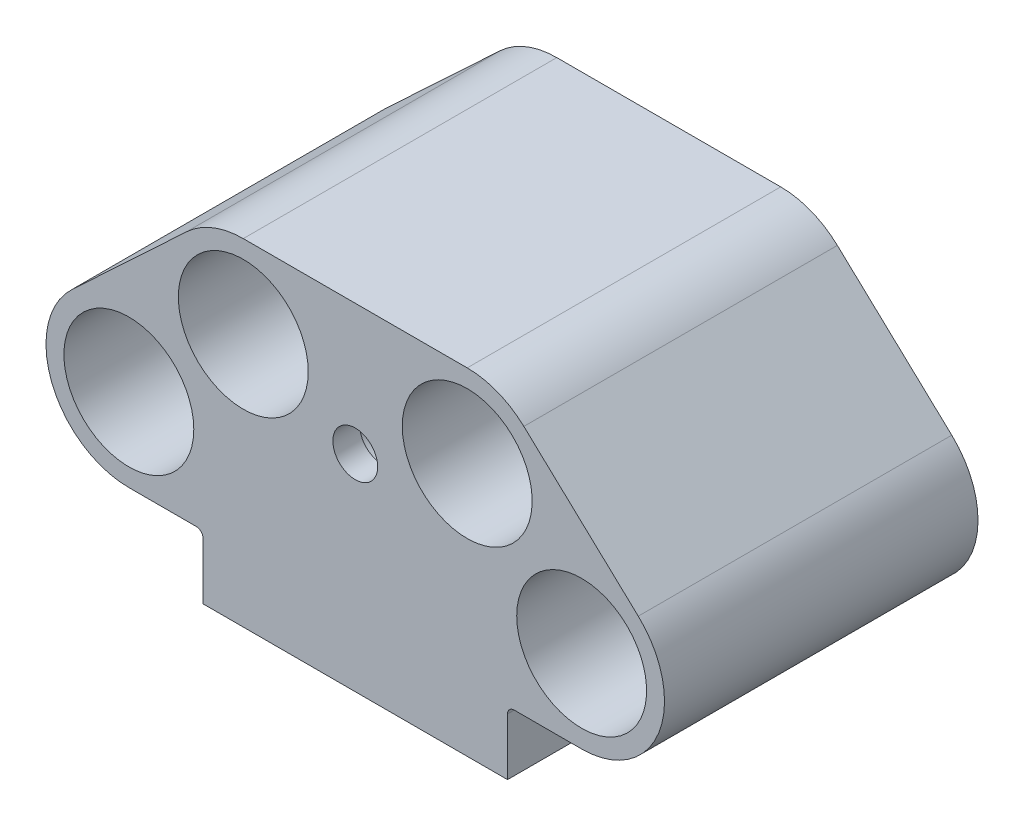
SolidWorks part; units mm, degrees
ref_plane "Front Plane" through (0, 0, 0) normal (0, 0, 1) x (1, 0, 0)
ref_plane "Top Plane" through (0, 0, 0) normal (0, 1, 0) x (1, 0, 0)
ref_plane "Right Plane" through (0, 0, 0) normal (1, 0, 0) x (0, 0, -1)
sketch "Sketch1" plane through (0, 0, 0) normal (0, 0, 1) x (1, 0, 0)
  line L0 (-11.9595, 12.7758) -> (-50.7466, -23.5332) construction
  line L1 (11.9595, 12.7758) -> (50.7466, -23.5332) construction
  line L2 (-11.9595, 12.7758) -> (11.9595, 12.7758) construction
  line L3 (-50.7466, -23.5332) -> (50.7466, -23.5332) construction
  line L4 (-17.5, -2) -> (17.5, -2) construction
  line L5 (0, 0) -> (0, -2) construction
  line L6 (-17.5, -2) -> (-17.5, 4) construction
  line L7 (-17.5, 4) -> (-20.5, 4) construction
  line L8 (-20.5, 4) -> (-20.5, -5) construction
  line L9 (-20.5, -5) -> (20.5, -5) construction
  line L10 (20.5, -5) -> (20.5, 4) construction
  line L11 (20.5, 4) -> (17.5, 4) construction
  line L12 (17.5, 4) -> (17.5, -2) construction
  line L13 (0, -2) -> (0, 40.1846) construction
  line L14 (-25.2758, 14.3506) -> (-12.5, 26.3101) construction
  line L15 (-31.5972, 21.1034) -> (-18.8215, 33.063)
  line L16 (-25.2758, 5.1006) -> (-17.75, 5.1006)
  line L17 (-17, 4.3506) -> (-17, -2)
  line L18 (-17, -2) -> (0, -2)
  line L19 (-12.5, 35.5601) -> (0, 35.5601)
  line L20 (0, 35.5601) -> (0, -2)
  circle A0 centre (0, 0) radius 17.5 construction
  circle A1 centre (-25.2758, 14.3506) radius 7.25
  circle A2 centre (-12.5, 26.3101) radius 7.25
  circle A3 centre (-12.5, 26.3101) radius 9.25 construction
  circle A4 centre (-25.2758, 14.3506) radius 9.25 construction
  arc A5 (-17.75, 5.1006) -> (-17, 4.3506) centre (-17.75, 4.3506) cw
  arc A6 (-18.8215, 33.063) -> (-12.5, 35.5601) centre (-12.5, 26.3101) cw
  arc A7 (-25.2758, 5.1006) -> (-31.5972, 21.1034) centre (-25.2758, 14.3506) cw
  dimension "D1" = 35
  dimension "D8" = 14.5
  dimension "D10" = 3
  dimension "D11" = 2
  dimension "D13" = 0.75
  dimension "D2" = 93.78
  dimension "D3" = 35
  dimension "2" = 2
  dimension "D4" = 6
  dimension "D5" = 3
  dimension "D6" = 3
  dimension "D7" = 3
  dimension "D9" = 25
  dimension "D12" = 0.5
extrude "Boss-Extrude1" add sketch "Sketch1" along normal mid plane 35 contours A7 L16 A5 L17 L18 L20 L19 A6 L15 A2 A1 region at (-11.7265, 14.9745, 0)
mirror "Mirror1" about plane through (0, 0, 0) normal (1, 0, 0) of "Boss-Extrude1"
sketch "Sketch2" plane through (0, 0, -17.5) normal (0, 0, -1) x (-1, 0, 0)
  line L0 (0, -2) -> (0, 21) construction
  line L1 (17, -2) -> (-17, -2) construction
  circle A0 centre (0, 21) radius 2.5
  point P3 (0, 14.3571)
  dimension "D2" = 5
  dimension "D1" = 23
extrude "Cut-Extrude1" cut sketch "Sketch2" against normal through all
sketch "Sketch3" plane through (0, 0, -17.5) normal (0, 0, -1) x (-1, 0, 0)
  circle A0 centre (0, 21) radius 4
  dimension "D1" = 8
extrude "Cut-Extrude2" cut sketch "Sketch3" against normal offset from surface (29 mm away) 3 from offset 3 up to face at (-2.5, 21, 17.5) offset against normal yes
